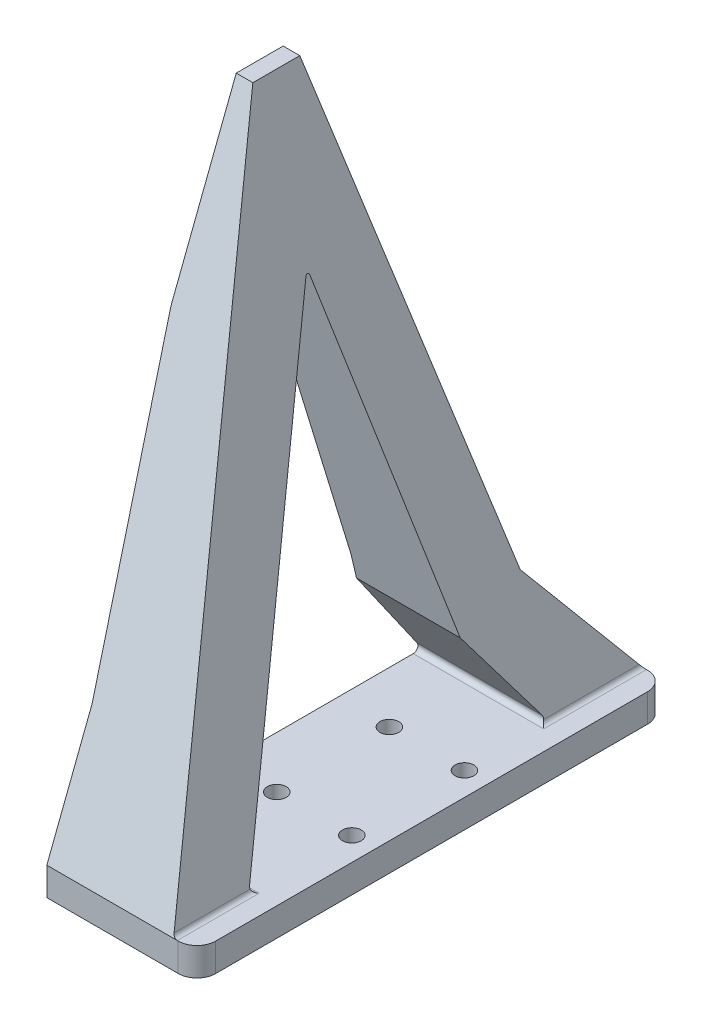
SolidWorks part; units mm, degrees
ref_plane "前视基准面" through (0, 0, 0) normal (0, 0, 1) x (1, 0, 0)
ref_plane "上视基准面" through (0, 0, 0) normal (0, 1, 0) x (1, 0, 0)
ref_plane "右视基准面" through (0, 0, 0) normal (1, 0, 0) x (0, 0, -1)
sketch "草图1" plane through (0, 0, 0) normal (0, 1, 0) x (1, 0, 0)
  line L0 (2.75, 0) -> (0, 0) construction
  line L1 (-9.25, 25) -> (7.25, 25)
  line L2 (-9.25, 25) -> (-9.25, -25)
  line L3 (-9.25, -25) -> (7.25, -25)
  line L4 (9.25, 23) -> (9.25, -23)
  line L5 (-9.25, 25) -> (9.25, -25) construction
  line L6 (-9.25, -25) -> (9.25, 25) construction
  line L7 (-1.25, 6) -> (6.75, 6) construction
  line L8 (-1.25, 6) -> (-1.25, -6) construction
  line L9 (-1.25, -6) -> (6.75, -6) construction
  line L10 (6.75, 6) -> (6.75, -6) construction
  line L11 (-1.25, 6) -> (6.75, -6) construction
  line L12 (-1.25, -6) -> (6.75, 6) construction
  circle A0 centre (-1.25, 6) radius 1
  circle A1 centre (-1.25, -6) radius 1
  circle A2 centre (6.75, -6) radius 1
  circle A3 centre (6.75, 6) radius 1
  arc A5 (7.25, -25) -> (9.25, -23) centre (7.25, -23) ccw
  arc A6 (7.25, 25) -> (9.25, 23) centre (7.25, 23) cw
  point P0 (0, 0)
  point P6 (2.75, 0)
  dimension "D3" = 2
  dimension "D1" = 12
  dimension "D2" = 8
  dimension "D4" = 8
  dimension "D5" = 5
  dimension "D6" = 50
extrude "凸台-拉伸1" add sketch "草图1" along normal blind 3
sketch "草图2" plane through (0, 3, 0) normal (0, 1, 0) x (1, 0, 0)
  line L0 (-9.25, -25) -> (7.25, -25) construction
  line L1 (6.7578, -25) -> (-9.25, -25)
  line L2 (6.7578, -25) -> (6.7578, 25)
  line L3 (6.7578, 25) -> (-9.25, 25)
  line L4 (-9.25, -25) -> (-9.25, 25)
  line L5 (6.7578, -25) -> (-9.25, 25) construction
  line L6 (6.7578, 25) -> (-9.25, -25) construction
  point P0 (-1.2461, 0)
extrude "凸台-拉伸2" add sketch "草图2" along normal blind 80
sketch "草图3" plane through (6.7578, 0, 0) normal (1, 0, 0) x (0, 0, -1)
  line L2 (0, 0) -> (0, 36.8077) construction
  line L4 (0, 47) -> (-17, 3)
  line L5 (-25, 3) -> (-7, 3) construction
  line L6 (25, 3) -> (15, 15.5)
  line L8 (15, 15.5) -> (3.1818, 63)
  line L10 (15, 3) -> (8, 13)
  line L11 (7, 3) -> (25, 3) construction
  line L13 (8, 13) -> (0, 47)
  line L14 (15, 3) -> (-17, 3)
  line L15 (25, 3) -> (63.3284, 3)
  line L16 (63.3284, 3) -> (63.3284, 88.4369)
  line L17 (63.3284, 88.4369) -> (-37.68, 88.4369)
  line L18 (-37.68, 88.4369) -> (-37.68, 3)
  line L19 (-37.68, 3) -> (-25, 3)
  line L20 (-25, 3) -> (-1.8182, 63)
  line L21 (3.1818, 63) -> (-1.8182, 63)
  line L22 (-23, 0) -> (23, 0) construction
  dimension "D1" = 8
  dimension "D2" = 10
  dimension "D3" = 5
  dimension "D4" = 60
  dimension "D5" = 8
  dimension "D6" = 13
  dimension "D7" = 15
  dimension "D8" = 15.5
  dimension "D9" = 47
extrude "切除-拉伸1" cut sketch "草图3" against normal through all
sketch "草图4" plane through (0, 0, -25) normal (0, 0, -1) x (-1, 0, 0)
  line L0 (-6.7578, 3) -> (8.4076, 64.7421)
  line L2 (8.4076, 64.7421) -> (-6.7578, 64.7421)
  line L3 (-6.7578, 64.7421) -> (-6.7578, 3)
  dimension "D1" = 103.8
extrude "切除-拉伸2" cut sketch "草图4" against normal through all
sketch "草图5" plane through (-9.25, 0, 0) normal (-1, 0, 0) x (0, 0, 1)
  line L0 (0, 47) -> (-8, 13)
  line L1 (-8, 13) -> (-15, 3)
  line L2 (-15, 3) -> (17, 3)
  line L3 (17, 3) -> (0, 47)
  line L4 (-3.1818, 63) -> (-15, 15.5)
  line L5 (-15, 15.5) -> (-25, 3)
  line L6 (-25, 3) -> (-25, 0)
  line L7 (-25, 0) -> (25, 0)
  line L8 (25, 0) -> (25, 3)
  line L9 (25, 3) -> (1.8182, 63)
  line L10 (1.8182, 63) -> (-3.1818, 63)
extrude "凸台-拉伸3" add sketch "草图5" along normal blind 3
sketch "草图6" plane through (0, 0, -25) normal (0, 0, -1) x (-1, 0, 0)
  line L0 (9.75, 65) -> (9.75, 45)
  line L1 (12.25, 63) -> (12.25, 15.5) construction
  line L2 (9.75, 45) -> (6.75, 15.5)
  line L3 (12.25, 15.5) -> (-3.6875, 15.5) construction
  line L4 (6.75, 15.5) -> (6.75, 0)
  line L5 (-7.25, 0) -> (12.25, 0) construction
  line L6 (6.75, 0) -> (15.0651, 0)
  line L7 (15.0651, 0) -> (15.0651, 65)
  line L8 (15.0651, 65) -> (9.75, 65)
  line L9 (12.25, 63) -> (7.9797, 63) construction
  dimension "D1" = 2.5
  dimension "D2" = 20
  dimension "D3" = 5.5
  dimension "D4" = 18
extrude "切除-拉伸3" cut sketch "草图6" against normal through all
fillet "圆角1" radius 0.5 4 edges at (0.0039, 3, 17) (0.0039, 3, -15) (6.7578, 3, 21) (6.7578, 3, -20)
fillet "圆角2" radius 0.2 1 edges at (-6.8998, 47, 0)
